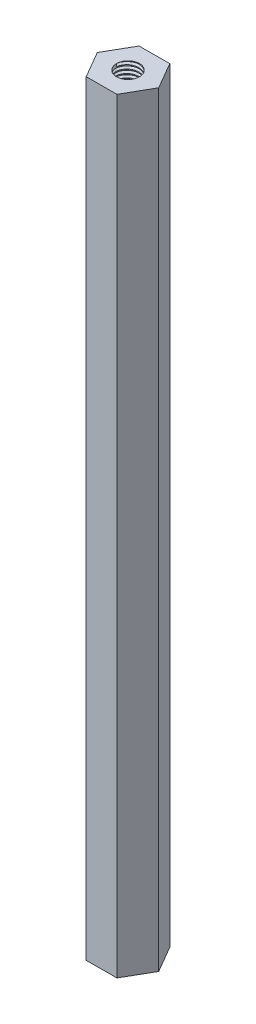
SolidWorks part; units mm, degrees
ref_plane "前视基准面" through (0, 0, 0) normal (0, 0, 1) x (1, 0, 0)
ref_plane "上视基准面" through (0, 0, 0) normal (0, 1, 0) x (1, 0, 0)
ref_plane "右视基准面" through (0, 0, 0) normal (1, 0, 0) x (0, 0, -1)
sketch "草图1" plane through (0, 0, 0) normal (0, 1, 0) x (1, 0, 0)
  line L1 (2.0098, -3.4584) -> (4, 0.0114)
  line L2 (4, 0.0114) -> (1.9902, 3.4698)
  line L3 (1.9902, 3.4698) -> (-2.0098, 3.4584)
  line L4 (-2.0098, 3.4584) -> (-4, -0.0114)
  line L5 (-4, -0.0114) -> (-1.9902, -3.4698)
  line L6 (-1.9902, -3.4698) -> (2.0098, -3.4584)
  circle A0 centre (0, 0) radius 3.4641 construction
  dimension "D1" = 4
extrude "凸台-拉伸1" add sketch "草图1" along normal blind 100
sketch "草图2" plane through (0, 0, 0) normal (0, -1, 0) x (1, 0, 0)
  circle A0 centre (0, 0) radius 1.5
  dimension "D1" = 3
extrude "切除-拉伸1" cut sketch "草图2" against normal blind 10
sketch "草图3" plane through (0, 100, 0) normal (0, 1, 0) x (1, 0, 0)
  circle A0 centre (0, 0) radius 1.5
  dimension "D1" = 3
extrude "切除-拉伸2" cut sketch "草图3" against normal blind 10
thread "螺纹线1" pitch 0.5 method cut profile "螺纹线轮廓1" start angle 0, offset 0, length 8, pitch 0.5, diameter 3
ref_plane "基准面1" through (1.5, 0, 0) normal (0, 0, 1) x (1, 0, 0)
sketch "螺纹线轮廓1" plane through (1.5, 0, 0) normal (0, 0, 1) x (1, 0, 0)
  line L0 (0, 0) -> (0, 0.5) construction
  line L1 (0, 0) -> (0.2706, 0.1562)
  line L2 (0.2706, 0.1562) -> (0.2706, 0.2187)
  line L3 (0.2706, 0.2187) -> (0, 0.375)
  line L4 (0.2706, 0.1875) -> (0, 0.1875) construction
  line L11 (0, 0) -> (0, 0.375)
  point P2 (0, 0)
  dimension "Pitch" = 0.5
  dimension "Profile_Angle" = 60
  dimension "Profile_Land" = 0.0625
  dimension "Profile_Height" = 0.2706
thread "螺纹线2" pitch 0.5 method cut profile "螺纹线轮廓2" start angle 0, offset 0, length 8, pitch 0.5, diameter 3
ref_plane "基准面2" through (-1.5, 100, 0) normal (0, 0, 1) x (-1, 0, 0)
sketch "螺纹线轮廓2" plane through (-1.5, 100, 0) normal (0, 0, 1) x (-1, 0, 0)
  line L0 (0, 0) -> (0, 0.5) construction
  line L1 (0, 0) -> (0.2706, 0.1562)
  line L2 (0.2706, 0.1562) -> (0.2706, 0.2187)
  line L3 (0.2706, 0.2187) -> (0, 0.375)
  line L4 (0.2706, 0.1875) -> (0, 0.1875) construction
  line L11 (0, 0) -> (0, 0.375)
  point P2 (0, 0)
  dimension "Pitch" = 0.5
  dimension "Profile_Angle" = 60
  dimension "Profile_Land" = 0.0625
  dimension "Profile_Height" = 0.2706
